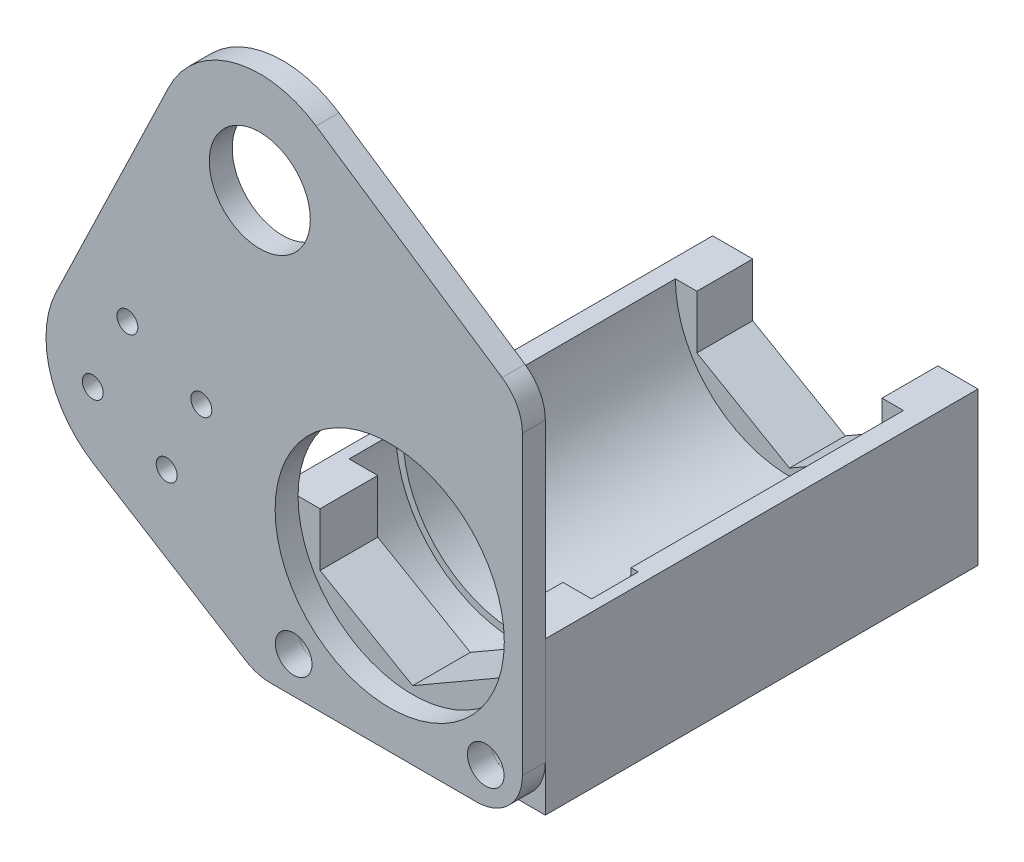
SolidWorks part; units mm, degrees
note: The reader was unsure of these and kept them because the rebuilt part matched: shared geometry of "Sketch1<3>", "Sketch1<5>", "Sketch1<4>".
ref_plane "Front Plane" through (0, 0, 0) normal (0, 0, 1) x (1, 0, 0)
ref_plane "Top Plane" through (0, 0, 0) normal (0, 1, 0) x (1, 0, 0)
ref_plane "Right Plane" through (0, 0, 0) normal (1, 0, 0) x (0, 0, -1)
sketch "Sketch1" plane through (0, 0, 0) normal (0, 0, 1) x (1, 0, 0)
  line L0 (-12.827, 0) -> (-18.3833, 0)
  line L1 (0, 14.8113) -> (-12.827, 7.4057)
  line L2 (-12.827, 7.4057) -> (-12.827, -7.4057)
  line L3 (-12.827, -7.4057) -> (0, -14.8113)
  line L4 (0, -14.8113) -> (12.827, -7.4057)
  line L5 (12.827, -7.4057) -> (12.827, 7.4057)
  line L6 (12.827, 7.4057) -> (0, 14.8113)
  line L7 (-18.3833, 0) -> (-18.3833, -21.1613)
  line L8 (-18.3833, -21.1613) -> (18.3833, -21.1613)
  line L9 (18.3833, -21.1613) -> (18.3833, 0)
  line L10 (18.3833, 0) -> (12.827, 0)
  circle A0 centre (0, 0) radius 12.827 construction
  circle A3 centre (0, 0) radius 16.7957
  circle A4 centre (0, 0) radius 15.7988
  circle A5 centre (-13.3032, -16.0813) radius 2.54 construction
  circle A6 centre (13.3033, -16.0813) radius 2.54 construction
  circle A7 centre (-13.3032, -16.0813) radius 2.54
  circle A8 centre (13.3033, -16.0813) radius 2.54
  dimension "D1" = 25.654
  dimension "D4" = 33.5915
  dimension "D5" = 31.5976
  dimension "D2" = 36.7665
  dimension "D3" = 6.35
extrude "Boss-Extrude1" add sketch "Sketch1" against normal blind 7.9926 contours L0 A4 L10 L5 L4 L3 L2 | A4 L0 A3 L10 | A3 L0 L7 L8 L9 L10
extrude "Boss-Extrude2" add sketch "Sketch1<3>" against normal blind 6.477 from surface at -7.9926
sketch "Sketch1<3>" plane through (0, 0, 0) normal (0, 0, 1) x (1, 0, 0) same geometry as "Sketch1"
extrude "Boss-Extrude4" add sketch "Sketch1<5>" along normal blind 7.7386 from offset 59.944 separate body contours L0 A4 L10 L5 L4 L3 L2 | A4 L0 A3 L10 | A3 L0 L7 L8 L9 L10 offset against normal yes
sketch "Sketch1<5>" plane through (0, 0, 0) normal (0, 0, 1) x (1, 0, 0) same geometry as "Sketch1"
extrude "Boss-Extrude3" add sketch "Sketch1<4>" against normal up to surface (37.7358 mm away) from surface at -14.4696 contours A3 L0 L7 L8 L9 L10 | A4 L0 A3 L10
sketch "Sketch1<4>" plane through (0, 0, 0) normal (0, 0, 1) x (1, 0, 0) same geometry as "Sketch1"
combine bodies "Combine1" operation type add bodies to combine 104 105
sketch "Sketch2" plane through (0, 0, 0) normal (0, 0, 1) x (1, 0, 0)
  line L0 (-18.3833, -21.1613) -> (18.3833, -21.1613) construction
  line L1 (-18.3833, 0) -> (-18.3833, -21.1613) construction
  line L2 (0, -39.8146) -> (0, 39.7753) construction
  line L3 (18.3833, -21.1613) -> (-18.3833, -21.1613)
  line L4 (18.3833, -21.1613) -> (18.3833, 29.6387)
  line L5 (-41.1466, 2.0448) -> (-26.0999, 7.485) construction
  line L6 (-12.5, 34.6981) -> (12.5, 34.6981) construction
  line L7 (-12.5, 34.6981) -> (-12.5, 39.6981) construction
  line L8 (-12.5, 39.6981) -> (12.5, 39.6981) construction
  line L9 (12.5, 34.6981) -> (12.5, 39.6981) construction
  line L10 (-12.5, 34.6981) -> (12.5, 39.6981) construction
  line L11 (-12.5, 39.6981) -> (12.5, 34.6981) construction
  line L12 (-36.3434, 12.2882) -> (-30.9031, -2.7585) construction
  line L13 (-33.6232, 4.7649) -> (-18, 37.1981) construction
  line L14 (-41.0019, -7.127) -> (-18.3833, -21.1613)
  line L15 (-46.2317, 10.8384) -> (-30.6084, 43.2716)
  line L16 (-10.2022, 48.8194) -> (18.3833, 29.6387)
  circle A0 centre (-13.3032, -16.0813) radius 2.54
  circle A1 centre (13.3033, -16.0813) radius 2.54
  circle A2 centre (0, -0.0196) radius 7.493 construction
  circle A3 centre (0, -0.0196) radius 7.493 construction
  circle A4 centre (0, -0.0196) radius 15.875
  circle A5 centre (-18, 37.1981) radius 5.5 construction
  circle A6 centre (-33.6232, 4.7649) radius 7.645 construction
  circle A7 centre (-18, 37.1981) radius 7.645 construction
  arc A8 (-46.2317, 10.8384) -> (-41.0019, -7.127) centre (-33.6232, 4.7649) ccw
  arc A9 (-30.6084, 43.2716) -> (-10.2022, 48.8194) centre (-18, 37.1981) cw
  circle A10 centre (-18, 37.1981) radius 7
  circle A11 centre (-33.6232, 4.7649) radius 15.24 construction
  point P21 (0, 37.1981)
  point P30 (-33.6232, 4.7649)
  point P40 (-34.8932, 8.1082)
  dimension "D1" = 5.08
  dimension "D4" = 31.75
  dimension "D5" = 11
  dimension "D10" = 15.29
  dimension "D11" = 6.35
  dimension "D12" = 30.48
  dimension "D13" = 6.35
  dimension "D15" = 14
  dimension "D16" = 15.24
  dimension "D2" = 5.08
  dimension "D3" = 5.08
  dimension "D6" = 25
  dimension "D7" = 5
  dimension "D8" = 16
  dimension "D9" = 36
  dimension "D14" = 50.8
extrude "Boss-Extrude5" add sketch "Sketch2" along normal blind 3.175 separate body
hole_wizard "M3.5x0.6 Tapped Hole1" positions "3DSketch1" profile "Sketch3" tap size "M3.5x0.6" standard "ANSI Metric"
sketch3d "3DSketch1"
  point P0 (-60.903, -2.6151, 0)
  point P2 (-36.3434, 12.2882, 0)
  point P5 (-41.1466, 2.0448, 0)
  point P8 (-30.9031, -2.7585, 0)
  point P11 (-26.0999, 7.485, 0)
sketch "Sketch3" plane through (-26.0999, 7.485, 0) normal (1, 0, 0) x (0, 1, 0)
  line L0 (0, 0) -> (0, 3.175)
  line L1 (0, 3.175) -> (1.45, 3.175)
  line L2 (1.45, 3.175) -> (1.45, 0)
  line L5 (1.45, 0) -> (0, 0)
  line L11 (0, -6.35) -> (0, 107.95) construction
  dimension "Thru Tap Drill Dia." = 2.9
  dimension "Thru Tap Drill Depth" = 3.175
cosmetic thread "Hole Thread1" parameters "D2"=3.5
cosmetic thread "Hole Thread2" parameters "D2"=3.5
cosmetic thread "Hole Thread4" parameters "D2"=3.5
cosmetic thread "Hole Thread5" parameters "D2"=3.5
fillet "Fillet1" radius 6.35 3 edges at (-18.3833, -21.1613, 1.5875) (18.3833, -21.1613, 1.5875) (18.3833, 29.6387, 1.5875)
split "Split1" bodies to split 106 108 resulting bodies 109 110
equation "\"D4@Sketch1\"=1.3125in + 0.010"
equation "\"D5@Sketch1\"=1.234in + 0.010"
equation "\"D2@Sketch1\"=\"D4@Sketch1\"+0.125"
equation "\"D1@Sketch1\"= 1.00in + 0.010"
equation "\"D1@Boss-Extrude4\"=0.31467in - 0.010in"
